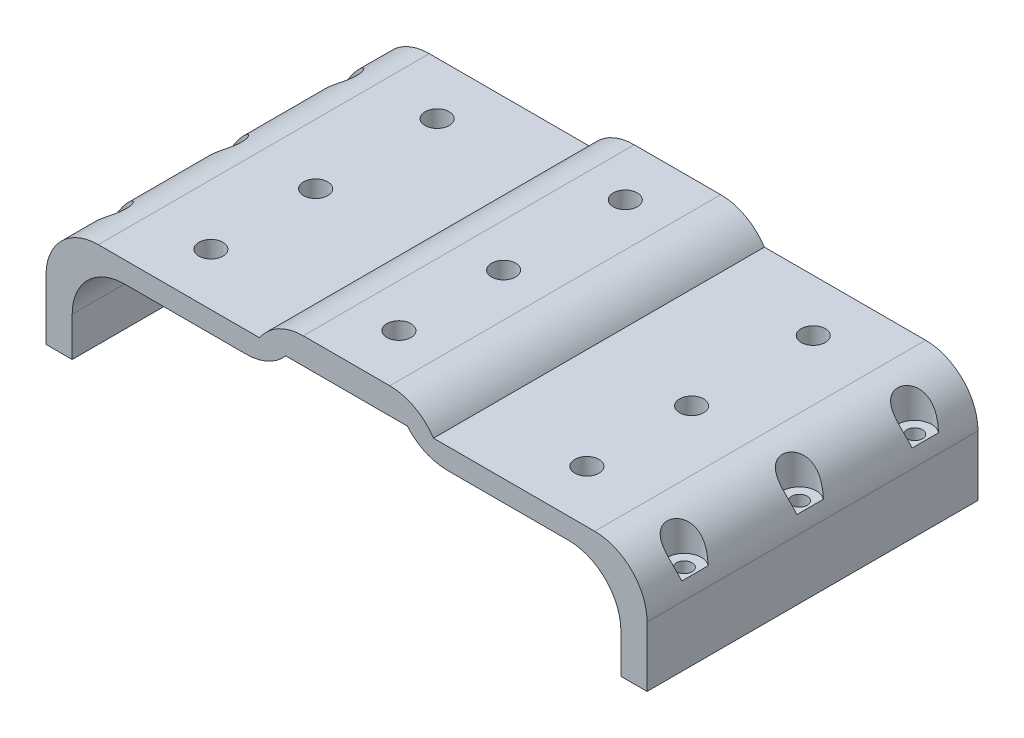
SolidWorks part; units mm, degrees
ref_plane "Front Plane" through (0, 0, 0) normal (0, 0, 1) x (1, 0, 0)
ref_plane "Top Plane" through (0, 0, 0) normal (0, 1, 0) x (1, 0, 0)
ref_plane "Right Plane" through (0, 0, 0) normal (1, 0, 0) x (0, 0, -1)
sketch "Sketch1" plane through (0, 0, 0) normal (0, 0, 1) x (1, 0, 0)
  line L0 (0, 0) -> (5, 0)
  line L4 (109.8, 0) -> (114.8, 0)
  line L5 (114.8, 0) -> (114.8, 21.5)
  line L7 (0, 21.5) -> (0, 0)
  line L8 (22.5, 21.5) -> (0, 21.5)
  line L9 (22.5, 21.5) -> (40.7918, 21.5)
  line L10 (40.7918, 21.5) -> (40.7918, 26)
  line L11 (40.7918, 26) -> (74.0082, 26)
  line L12 (74.0082, 26) -> (74.0082, 21.5)
  line L13 (74.0082, 21.5) -> (92.3, 21.5)
  line L14 (92.3, 21.5) -> (114.8, 21.5)
  line L15 (5, 0) -> (5, 17.5)
  line L16 (5, 17.5) -> (22.5, 17.5)
  line L17 (22.5, 17.5) -> (45.7918, 17.5)
  line L18 (45.7918, 17.5) -> (45.7918, 21)
  line L19 (45.7918, 21) -> (57.4, 21)
  line L20 (57.4, 21) -> (69.0082, 21)
  line L21 (69.0082, 21) -> (69.0082, 17.5)
  line L22 (69.0082, 17.5) -> (92.3, 17.5)
  line L23 (92.3, 17.5) -> (109.8, 17.5)
  line L24 (109.8, 17.5) -> (109.8, 0)
  line L25 (5, 0) -> (109.8, 0) construction
  circle A0 centre (22.5, 0) radius 17.5 construction
  circle A1 centre (92.3, 0) radius 17.5 construction
  circle A2 centre (57.4, 0) radius 21 construction
  dimension "D3" = 35
  dimension "D4" = 42
  dimension "D1" = 5
  dimension "D2" = 114.8
  dimension "D5" = 5
  dimension "D6" = 5
  dimension "D7" = 21.5
  dimension "D8" = 5
extrude "Boss-Extrude1" add sketch "Sketch1" along normal blind 63.2 contours L7 L0 L15 L16 L17 L18 L19 L20 L21 L22 L23 L24 L4 L5 L14 L13 L12 L11 L10 L9 L8
fillet "Fillet1" radius 10 4 edges at (109.8, 17.5, 31.6) (5, 17.5, 31.6) (114.8, 21.5, 31.6) (0, 21.5, 31.6)
fillet "Fillet2" radius 10 2 edges at (40.7918, 26, 31.6) (74.0082, 26, 31.6)
fillet "Fillet3" radius 10 2 edges at (45.7918, 17.5, 31.6) (69.0082, 17.5, 31.6)
sketch "Sketch2" plane through (0, 26, 0) normal (0, 1, 0) x (1, 0, 0)
  line L0 (57.4, 0) -> (57.4, -63.2) construction
  line L1 (49.1435, 0) -> (65.6565, 0) construction
  line L2 (49.1435, -63.2) -> (65.6565, -63.2) construction
  line L3 (21.5, 0) -> (21.5, -63.2) construction
  line L6 (93.3, 0) -> (93.3, -63.2) construction
  line L9 (5, -63.2) -> (5, 0) construction
  line L10 (5, -63.2) -> (5, 0) construction
  line L11 (109.8, -63.2) -> (109.8, 0) construction
  line L12 (109.8, -63.2) -> (109.8, 0) construction
  line L13 (40.7918, -63.2) -> (10, -63.2) construction
  line L14 (10, 0) -> (40.7918, 0) construction
  line L15 (21.5, -10) -> (122.7833, -10) construction
  line L16 (21.5, -33.2) -> (122.7833, -33.2) construction
  line L17 (21.5, -53.2) -> (122.7833, -53.2) construction
  circle A0 centre (57.4, -9.9642) radius 2.3
  circle A1 centre (57.4, -33.2) radius 2.3
  circle A2 centre (57.4, -53.2) radius 2.3
  circle A3 centre (21.5, -10) radius 2.3
  circle A4 centre (93.3, -9.9642) radius 2.3
  circle A5 centre (93.3, -33.2) radius 2.3
  circle A6 centre (93.3, -53.2) radius 2.3
  circle A7 centre (21.5, -53.2) radius 2.3
  circle A8 centre (21.5, -33.2) radius 2.3
  point P16 (93.3, -53.2)
  point P39 (57.4, -53.2)
  point P41 (57.4, -33.2)
  point P42 (93.3, -33.2)
  dimension "D1" = 4.6
  dimension "D2" = 16.5
  dimension "D3" = 16.5
  dimension "D4" = 10
  dimension "D5" = 20
  dimension "D6" = 10
extrude "Cut-Extrude1" cut sketch "Sketch2" against normal up to next
sketch "Sketch3" plane through (0, 0, 0) normal (0, -1, 0) x (1, 0, 0)
  line L0 (2.5, 0) -> (2.5, 63.2) construction
  line L1 (0, 0) -> (5, 0) construction
  line L2 (0, 63.2) -> (5, 63.2) construction
  line L3 (57.4, 63.2) -> (57.4, -4.5196) construction
  line L4 (45.7918, 63.2) -> (69.0082, 63.2) construction
  circle A0 centre (2.5, 31.6) radius 1.5
  circle A1 centre (2.5, 53.6) radius 1.5
  circle A2 centre (2.5, 9.6) radius 1.5
  circle A3 centre (112.3, 9.6) radius 1.5
  circle A4 centre (112.3, 53.6) radius 1.5
  circle A5 centre (112.3, 31.6) radius 1.5
  point P18 (-5.686, 34.9148)
  dimension "D1" = 3
  dimension "D2" = 22
  dimension "D3" = 22
extrude "Cut-Extrude2" cut sketch "Sketch3" against normal through all
sketch "Sketch4" plane through (0, 21.5, 0) normal (0, 1, 0) x (1, 0, 0)
  line L0 (57.4, 0) -> (57.4, -72.1972) construction
  line L1 (49.1435, 0) -> (65.6565, 0) construction
  circle A0 centre (2.5, -9.6) radius 3.25
  circle A1 centre (2.5, -31.6) radius 3.25
  circle A2 centre (2.5, -53.6) radius 3.25
  circle A3 centre (112.3, -53.6) radius 3.25
  circle A4 centre (112.3, -31.6) radius 3.25
  circle A5 centre (112.3, -9.6) radius 3.25
  dimension "D1" = 6.5
extrude "Cut-Extrude3" cut sketch "Sketch4" against normal blind 7
